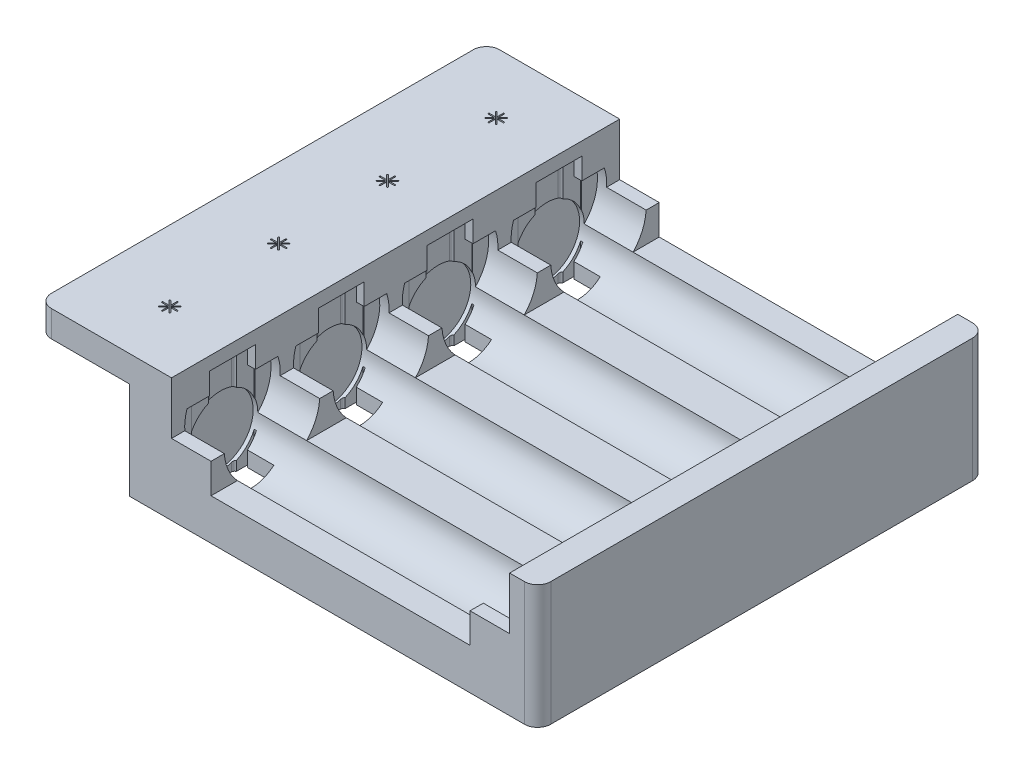
SolidWorks part; units mm, degrees
ref_plane "前视基准面" through (0, 0, 0) normal (0, 0, 1) x (1, 0, 0)
ref_plane "上视基准面" through (0, 0, 0) normal (0, 1, 0) x (1, 0, 0)
ref_plane "右视基准面" through (0, 0, 0) normal (1, 0, 0) x (0, 0, -1)
other "Configuration Table"
sketch "草图1" plane through (0, 0, 0) normal (0, 1, 0) x (1, 0, 0)
  line L1 (1.4739, 27.4794) -> (61.3689, 27.4794)
  line L2 (1.4739, 27.4794) -> (1.4739, -40.5206)
  line L3 (1.4739, -40.5206) -> (61.3689, -40.5206)
  line L4 (63.3689, 25.4794) -> (63.3689, -38.5206)
  arc A0 (61.3689, -40.5206) -> (63.3689, -38.5206) centre (61.3689, -38.5206) ccw
  arc A1 (61.3689, 27.4794) -> (63.3689, 25.4794) centre (61.3689, 25.4794) cw
  point P6 (63.3689, -40.5206)
  point P9 (63.3689, 27.4794)
  dimension "D3" = 2
  dimension "D1" = 68
  dimension "D2" = 61.895
extrude "凸台-拉伸1" add sketch "草图1" along normal blind 9.25
sketch "草图2" plane through (0, 9.25, 0) normal (0, 1, 0) x (1, 0, 0)
  line L0 (63.3689, -36.6531) -> (63.3689, -41.0442) construction
  line L1 (63.3689, -38.5206) -> (63.3689, 25.4794) construction
  line L2 (60.5082, -40.5206) -> (64.183, -40.5206) construction
  line L3 (1.4739, -40.5206) -> (61.3689, -40.5206) construction
  line L4 (54.4739, -29.5706) -> (54.4739, -32.9706) construction
  line L5 (63.3689, -40.5206) -> (54.4739, -40.5206) construction
  line L6 (63.3689, -40.5206) -> (63.3689, -31.2706) construction
  line L7 (63.3689, -31.2706) -> (54.4739, -31.2706) construction
  line L8 (54.4739, -40.5206) -> (54.4739, -31.2706) construction
  line L9 (54.9239, -29.5706) -> (54.9239, -32.9706)
  line L10 (54.0239, -29.5706) -> (54.0239, -32.9706)
  line L11 (54.4739, -13.0606) -> (54.4739, -16.4606) construction
  line L12 (54.9239, -13.0606) -> (54.9239, -16.4606)
  line L13 (54.0239, -13.0606) -> (54.0239, -16.4606)
  line L14 (54.4739, 3.4494) -> (54.4739, 0.0494) construction
  line L15 (54.9239, 3.4494) -> (54.9239, 0.0494)
  line L16 (54.0239, 3.4494) -> (54.0239, 0.0494)
  line L17 (54.4739, 19.9594) -> (54.4739, 16.5594) construction
  line L18 (54.9239, 19.9594) -> (54.9239, 16.5594)
  line L19 (54.0239, 19.9594) -> (54.0239, 16.5594)
  arc A0 (54.9239, -29.5706) -> (54.0239, -29.5706) centre (54.4739, -29.5706) ccw
  arc A1 (54.0239, -32.9706) -> (54.9239, -32.9706) centre (54.4739, -32.9706) ccw
  arc A2 (54.9239, -13.0606) -> (54.0239, -13.0606) centre (54.4739, -13.0606) ccw
  arc A3 (54.0239, -16.4606) -> (54.9239, -16.4606) centre (54.4739, -16.4606) ccw
  arc A4 (54.9239, 3.4494) -> (54.0239, 3.4494) centre (54.4739, 3.4494) ccw
  arc A5 (54.0239, 0.0494) -> (54.9239, 0.0494) centre (54.4739, 0.0494) ccw
  arc A6 (54.9239, 19.9594) -> (54.0239, 19.9594) centre (54.4739, 19.9594) ccw
  arc A7 (54.0239, 16.5594) -> (54.9239, 16.5594) centre (54.4739, 16.5594) ccw
  point P8 (63.3689, -40.5206)
  point P15 (54.4739, -31.2706)
  point P20 (54.4739, -29.1206)
  point P21 (54.4739, -33.4206)
  point P26 (54.4739, -14.7606)
  point P33 (54.4739, 1.7494)
  point P40 (54.4739, 18.2594)
  dimension "D3" = 0.45
  dimension "D1" = 8.895
  dimension "D2" = 9.25
  dimension "D4" = 4.3
  dimension "D5" = 4
extrude "切除-拉伸1" cut sketch "草图2" against normal blind 9.25
sketch "草图3" plane through (0, 9.25, 0) normal (0, 1, 0) x (1, 0, 0)
  line L0 (54.0239, -31.2706) -> (54.9239, -31.2706) construction
  line L1 (54.0239, -29.5706) -> (54.0239, -32.9706) construction
  line L2 (54.9239, -32.9706) -> (54.9239, -29.5706) construction
  line L3 (54.2989, -9.9356) -> (54.6489, -9.9356)
  line L4 (54.2989, -26.4456) -> (54.6489, -26.4456)
  line L5 (54.2989, -26.4456) -> (54.2989, -36.0956)
  line L6 (54.2989, -36.0956) -> (54.6489, -36.0956)
  line L7 (54.6489, -26.4456) -> (54.6489, -36.0956)
  line L8 (54.2989, -26.4456) -> (54.6489, -36.0956) construction
  line L9 (54.2989, -36.0956) -> (54.6489, -26.4456) construction
  line L10 (54.2989, -9.9356) -> (54.2989, -19.5856)
  line L11 (54.2989, -19.5856) -> (54.6489, -19.5856)
  line L12 (54.6489, -9.9356) -> (54.6489, -19.5856)
  line L13 (54.0239, -14.7606) -> (54.9239, -14.7606) construction
  line L14 (54.2989, -9.9356) -> (54.6489, -19.5856) construction
  line L15 (54.2989, -19.5856) -> (54.6489, -9.9356) construction
  line L16 (54.2989, 6.5744) -> (54.6489, 6.5744)
  line L17 (54.2989, 6.5744) -> (54.2989, -3.0756)
  line L18 (54.2989, -3.0756) -> (54.6489, -3.0756)
  line L19 (54.6489, 6.5744) -> (54.6489, -3.0756)
  line L20 (54.0239, 1.7494) -> (54.9239, 1.7494) construction
  line L21 (54.2989, 6.5744) -> (54.6489, -3.0756) construction
  line L22 (54.2989, -3.0756) -> (54.6489, 6.5744) construction
  line L23 (54.2989, 23.0844) -> (54.6489, 23.0844)
  line L24 (54.2989, 23.0844) -> (54.2989, 13.4344)
  line L25 (54.2989, 13.4344) -> (54.6489, 13.4344)
  line L26 (54.6489, 23.0844) -> (54.6489, 13.4344)
  line L27 (54.0239, 18.2594) -> (54.9239, 18.2594) construction
  line L28 (54.2989, 23.0844) -> (54.6489, 13.4344) construction
  line L29 (54.2989, 13.4344) -> (54.6489, 23.0844) construction
  point P6 (54.4739, -31.2706)
  point P15 (54.4739, -14.7606)
  point P22 (54.4739, 1.7494)
  point P29 (54.4739, 18.2594)
  dimension "D1" = 0.35
  dimension "D2" = 9.65
extrude "切除-拉伸4" cut sketch "草图3" against normal blind 5.25
sketch "草图6" plane through (0, 9.25, 0) normal (0, 1, 0) x (1, 0, 0)
  line L0 (54.0239, -36.5206) -> (54.0239, -26.0206)
  point P3 (54.0239, -31.2706)
sketch "草图7" plane through (0, 0, 0) normal (0, -1, 0) x (1, 0, 0)
  line L5 (61.3689, -27.4794) -> (1.4739, -27.4794)
  line L6 (63.3689, -25.4794) -> (63.3689, 38.5206)
  line L7 (61.3689, 40.5206) -> (1.4739, 40.5206)
  line L8 (1.4739, -27.4794) -> (1.4739, 40.5206)
  arc A0 (63.3689, 38.5206) -> (61.3689, 40.5206) centre (61.3689, 38.5206) ccw
  arc A1 (61.3689, -27.4794) -> (63.3689, -25.4794) centre (61.3689, -25.4794) ccw
  point P2 (63.3689, -27.4794)
  point P8 (63.3689, -27.4794)
  dimension "D1" = 2
  dimension "D2" = 2
extrude "凸台-拉伸2" add sketch "草图7" against normal blind 13.5
sketch "草图9" plane through (0, 13.5, 0) normal (0, 1, 0) x (1, 0, 0)
  line L0 (54.4739, -32.9706) -> (54.4739, -29.5706) construction
  line L2 (54.0239, -32.9706) -> (54.0239, -29.5706)
  line L4 (54.9239, -32.9706) -> (54.9239, -29.5706)
  line L5 (63.3689, -40.5206) -> (54.4739, -40.5206) construction
  line L6 (63.3689, -40.5206) -> (63.3689, -31.2706) construction
  line L7 (63.3689, -31.2706) -> (54.4739, -31.2706) construction
  line L8 (54.4739, -40.5206) -> (54.4739, -31.2706) construction
  line L9 (54.4739, -16.4606) -> (54.4739, -13.0606) construction
  line L10 (54.0239, -16.4606) -> (54.0239, -13.0606)
  line L11 (54.9239, -16.4606) -> (54.9239, -13.0606)
  line L12 (54.4739, 0.0494) -> (54.4739, 3.4494) construction
  line L13 (54.0239, 0.0494) -> (54.0239, 3.4494)
  line L14 (54.9239, 0.0494) -> (54.9239, 3.4494)
  line L15 (54.4739, 16.5594) -> (54.4739, 19.9594) construction
  line L16 (54.0239, 16.5594) -> (54.0239, 19.9594)
  line L17 (54.9239, 16.5594) -> (54.9239, 19.9594)
  arc A0 (54.0239, -32.9706) -> (54.9239, -32.9706) centre (54.4739, -32.9706) ccw
  arc A1 (54.9239, -29.5706) -> (54.0239, -29.5706) centre (54.4739, -29.5706) ccw
  arc A2 (54.0239, -16.4606) -> (54.9239, -16.4606) centre (54.4739, -16.4606) ccw
  arc A3 (54.9239, -13.0606) -> (54.0239, -13.0606) centre (54.4739, -13.0606) ccw
  arc A4 (54.0239, 0.0494) -> (54.9239, 0.0494) centre (54.4739, 0.0494) ccw
  arc A5 (54.9239, 3.4494) -> (54.0239, 3.4494) centre (54.4739, 3.4494) ccw
  arc A6 (54.0239, 16.5594) -> (54.9239, 16.5594) centre (54.4739, 16.5594) ccw
  arc A7 (54.9239, 19.9594) -> (54.0239, 19.9594) centre (54.4739, 19.9594) ccw
  point P2 (54.4739, -31.2706)
  point P7 (54.4739, -29.1206)
  point P8 (63.3689, -40.5206)
  point P9 (63.3689, -40.5206)
  point P14 (54.4739, -33.4206)
  point P18 (54.4739, -14.7606)
  point P25 (54.4739, 1.7494)
  point P32 (54.4739, 18.2594)
  dimension "D3" = 0.45
  dimension "D1" = 8.895
  dimension "D2" = 9.25
  dimension "D4" = 4.3
extrude "切除-拉伸5" cut sketch "草图9" against normal blind 13.5
sketch "草图10" plane through (0, 13.5, 0) normal (0, 1, 0) x (1, 0, 0)
  line L0 (54.3222, -19.5856) -> (54.6256, -19.5856)
  line L2 (54.3222, -19.5856) -> (54.3222, -9.9356)
  line L3 (54.3222, -36.0956) -> (54.6256, -36.0956)
  line L4 (54.3222, -36.0956) -> (54.3222, -26.4456)
  line L5 (54.3222, -26.4456) -> (54.6256, -26.4456)
  line L6 (54.6256, -36.0956) -> (54.6256, -26.4456)
  line L7 (54.3222, -36.0956) -> (54.6256, -26.4456) construction
  line L8 (54.3222, -26.4456) -> (54.6256, -36.0956) construction
  line L9 (54.3222, -9.9356) -> (54.6256, -9.9356)
  line L10 (54.6256, -19.5856) -> (54.6256, -9.9356)
  line L11 (54.3222, -19.5856) -> (54.6256, -9.9356) construction
  line L12 (54.3222, -9.9356) -> (54.6256, -19.5856) construction
  line L13 (54.3222, -3.0756) -> (54.6256, -3.0756)
  line L14 (54.3222, -3.0756) -> (54.3222, 6.5744)
  line L15 (54.3222, 6.5744) -> (54.6256, 6.5744)
  line L16 (54.6256, -3.0756) -> (54.6256, 6.5744)
  line L17 (54.3222, -3.0756) -> (54.6256, 6.5744) construction
  line L18 (54.3222, 6.5744) -> (54.6256, -3.0756) construction
  line L19 (54.3222, 13.4344) -> (54.6256, 13.4344)
  line L20 (54.3222, 13.4344) -> (54.3222, 23.0844)
  line L21 (54.3222, 23.0844) -> (54.6256, 23.0844)
  line L22 (54.6256, 13.4344) -> (54.6256, 23.0844)
  line L23 (54.3222, 13.4344) -> (54.6256, 23.0844) construction
  line L24 (54.3222, 23.0844) -> (54.6256, 13.4344) construction
  point P3 (54.4739, -14.7606)
  point P5 (54.4739, -31.2706)
  point P13 (54.4739, 1.7494)
  point P18 (54.4739, 18.2594)
  dimension "D1" = 0.3034
extrude "切除-拉伸6" cut sketch "草图10" against normal blind 13.5
sketch "草图11" plane through (0, 13.5, 0) normal (0, 1, 0) x (1, 0, 0)
  line L0 (6.4592, -32.9706) -> (6.4592, -29.5706) construction
  line L1 (6.0092, -32.9706) -> (6.0092, -29.5706)
  line L2 (6.9092, -32.9706) -> (6.9092, -29.5706)
  line L3 (6.2927, -19.5856) -> (6.6256, -19.5856)
  line L4 (6.2927, -36.0956) -> (6.6256, -36.0956)
  line L5 (6.2927, -36.0956) -> (6.2927, -26.4456)
  line L6 (6.2927, -26.4456) -> (6.6256, -26.4456)
  line L7 (6.6256, -36.0956) -> (6.6256, -26.4456)
  line L8 (6.2927, -36.0956) -> (6.6256, -26.4456) construction
  line L9 (6.2927, -26.4456) -> (6.6256, -36.0956) construction
  line L10 (6.2927, -19.5856) -> (6.2927, -9.9356)
  line L11 (6.2927, -9.9356) -> (6.6256, -9.9356)
  line L12 (6.6256, -19.5856) -> (6.6256, -9.9356)
  line L13 (6.2927, -19.5856) -> (6.6256, -9.9356) construction
  line L14 (6.2927, -9.9356) -> (6.6256, -19.5856) construction
  line L15 (6.4592, -16.4606) -> (6.4592, -13.0606) construction
  line L16 (6.0092, -16.4606) -> (6.0092, -13.0606)
  line L17 (6.9092, -16.4606) -> (6.9092, -13.0606)
  line L18 (6.2927, -3.0756) -> (6.6256, -3.0756)
  line L19 (6.2927, -3.0756) -> (6.2927, 6.5744)
  line L20 (6.2927, 6.5744) -> (6.6256, 6.5744)
  line L21 (6.6256, -3.0756) -> (6.6256, 6.5744)
  line L22 (6.2927, -3.0756) -> (6.6256, 6.5744) construction
  line L23 (6.2927, 6.5744) -> (6.6256, -3.0756) construction
  line L24 (6.4592, 0.0494) -> (6.4592, 3.4494) construction
  line L25 (6.0092, 0.0494) -> (6.0092, 3.4494)
  line L26 (6.9092, 0.0494) -> (6.9092, 3.4494)
  line L27 (6.2927, 13.4344) -> (6.6256, 13.4344)
  line L28 (6.2927, 13.4344) -> (6.2927, 23.0844)
  line L29 (6.2927, 23.0844) -> (6.6256, 23.0844)
  line L30 (6.6256, 13.4344) -> (6.6256, 23.0844)
  line L31 (6.2927, 13.4344) -> (6.6256, 23.0844) construction
  line L32 (6.2927, 23.0844) -> (6.6256, 13.4344) construction
  line L33 (6.4592, 16.5594) -> (6.4592, 19.9594) construction
  line L34 (6.0092, 16.5594) -> (6.0092, 19.9594)
  line L35 (6.9092, 16.5594) -> (6.9092, 19.9594)
  arc A0 (6.0092, -32.9706) -> (6.9092, -32.9706) centre (6.4592, -32.9706) ccw
  arc A1 (6.9092, -29.5706) -> (6.0092, -29.5706) centre (6.4592, -29.5706) ccw
  arc A2 (6.0092, -16.4606) -> (6.9092, -16.4606) centre (6.4592, -16.4606) ccw
  arc A3 (6.9092, -13.0606) -> (6.0092, -13.0606) centre (6.4592, -13.0606) ccw
  arc A4 (6.0092, 0.0494) -> (6.9092, 0.0494) centre (6.4592, 0.0494) ccw
  arc A5 (6.9092, 3.4494) -> (6.0092, 3.4494) centre (6.4592, 3.4494) ccw
  arc A6 (6.0092, 16.5594) -> (6.9092, 16.5594) centre (6.4592, 16.5594) ccw
  arc A7 (6.9092, 19.9594) -> (6.0092, 19.9594) centre (6.4592, 19.9594) ccw
  point P2 (6.4592, -31.2706)
  point P7 (6.4592, -29.1206)
  point P8 (6.4592, -33.4206)
  point P9 (6.4592, -31.2706)
  point P19 (6.4592, -14.7606)
  point P24 (6.4592, -14.7606)
  point P31 (6.4592, 1.7494)
  point P36 (6.4592, 1.7494)
  point P43 (6.4592, 18.2594)
  point P48 (6.4592, 18.2594)
  dimension "D2" = 0.45
  dimension "D1" = 4.3
  dimension "D3" = 0
  dimension "D4" = 48
  dimension "D5" = 4
extrude "切除-拉伸7" cut sketch "草图11" against normal blind 13.5 contours L2 A1 L7 A0 | L5 A1 L1 A0 | A0 L5 L4 L7 | A1 L7 L6 L5 | A3 L12 L11 L10 | A2 L10 L3 L12 | L26 A5 L21 A4 | A7 L30 L29 L28 | A6 L28 L27 L30 | L28 A7 L34 A6 | L7 A1 L5 A0 | L12 A3 L10 A2 | L19 A5 L25 A4 | L16 A3 L17 A2 | L20 L21 L18 L19 | L35 A7 L34 A6 | L30 L29 L28 L27 region at (6.1547, 13.5, 31.2706) region at (6.4592, 13.5, 34.7529) region at (6.4592, 13.5, 31.2706) region at (6.4592, 13.5, 27.7884) region at (6.7637, 13.5, 31.2706) region at (6.4592, 13.5, 18.2429) region at (6.4592, 13.5, 14.7606) region at (6.4592, 13.5, 11.2784) region at (6.1547, 13.5, -1.7494) region at (6.7637, 13.5, -1.7494) region at (6.4592, 13.5, -14.7771) region at (6.1547, 13.5, -18.2594) region at (6.4592, 13.5, -21.7416)
sketch "草图13" plane through (0, 13.5, 0) normal (0, 1, 0) x (1, 0, 0)
  line L0 (6.2927, -36.0956) -> (6.2927, -40.5206) construction
  line L1 (61.3689, -40.5206) -> (1.4739, -40.5206) construction
  line L2 (6.6256, -36.0956) -> (6.6256, -40.5206) construction
  line L3 (54.3222, -36.0956) -> (54.3222, -40.5206) construction
  line L4 (54.6256, -36.0956) -> (54.6256, -40.5206) construction
sketch "草图14" plane through (0, 0, 40.5206) normal (0, 0, 1) x (1, 0, 0)
  line L0 (61.3689, 13.5) -> (1.4739, 13.5) construction
  line L1 (7.8256, 13.5) -> (53.1222, 13.5)
  line L2 (7.8256, 13.5) -> (7.8256, 6.25)
  line L3 (7.8256, 6.25) -> (53.1222, 6.25)
  line L4 (53.1222, 13.5) -> (53.1222, 6.25)
  point P6 (0, 0)
  dimension "D1" = 1.2
  dimension "D2" = 1.2
  dimension "D3" = 7.25
extrude "切除-拉伸8" cut sketch "草图14" against normal blind 78.5
sketch "草图15" plane through (0, 13.5, 0) normal (0, 1, 0) x (1, 0, 0)
  line L0 (7.8256, 27.4794) -> (7.8256, -40.5206) construction
  line L1 (7.8256, 27.4794) -> (7.8256, -40.5206) construction
  point P0 (7.8256, -31.2706)
  point P1 (7.8256, -14.7606)
  point P4 (7.8256, 1.7494)
  point P7 (7.8256, 18.2594)
ref_plane "基准面1" through (7.8256, 0, 0) normal (1, 0, 0) x (0, 0, -1)
sketch "草图17" plane through (7.8256, 0, 0) normal (1, 0, 0) x (0, 0, -1)
  circle A0 centre (-31.2706, 6.25) radius 5.25
  circle A1 centre (-14.7606, 6.25) radius 5.25
  circle A2 centre (1.7494, 6.25) radius 5.25
  circle A3 centre (18.2594, 6.25) radius 5.25
  dimension "D1" = 10.5
extrude "切除-拉伸9" cut sketch "草图17" along normal blind 46.5 and the other way blind 2.1105
sketch "草图18" plane through (0, 0, 0) normal (0, -1, 0) x (1, 0, 0)
  line L0 (6.6256, 34.7422) -> (6.6256, 27.7991)
  line L1 (6.6256, 34.7422) -> (10.6286, 34.7422)
  line L2 (6.6256, 27.7991) -> (10.6286, 27.7991)
  line L3 (10.6286, 34.7422) -> (10.6286, 27.7991)
  line L4 (6.6256, 36.0956) -> (6.6256, 33.3887) construction
  line L5 (6.6256, 29.1525) -> (6.6256, 26.4456) construction
  line L6 (6.6256, 18.2322) -> (6.6256, 11.2891)
  line L7 (6.6256, 18.2322) -> (10.6286, 18.2322)
  line L8 (10.6286, 18.2322) -> (10.6286, 11.2891)
  line L9 (6.6256, 11.2891) -> (10.6286, 11.2891)
  line L10 (6.6256, 1.7222) -> (6.6256, -5.2209)
  line L11 (6.6256, 1.7222) -> (10.6286, 1.7222)
  line L12 (10.6286, 1.7222) -> (10.6286, -5.2209)
  line L13 (6.6256, -5.2209) -> (10.6286, -5.2209)
  line L14 (6.6256, -14.7878) -> (6.6256, -21.7309)
  line L15 (6.6256, -14.7878) -> (10.6286, -14.7878)
  line L16 (10.6286, -14.7878) -> (10.6286, -21.7309)
  line L17 (6.6256, -21.7309) -> (10.6286, -21.7309)
extrude "切除-拉伸10" cut sketch "草图18" against normal blind 2.36
sketch "草图19" plane through (0, 0, 0) normal (0, -1, 0) x (1, 0, 0)
  line L0 (54.3222, 34.745) -> (54.3222, 27.7963)
  line L1 (54.3222, 34.745) -> (50.3222, 34.745)
  line L2 (54.3222, 27.7963) -> (50.3222, 27.7963)
  line L3 (50.3222, 34.745) -> (50.3222, 27.7963)
  line L4 (54.3222, 33.3943) -> (54.3222, 36.0956) construction
  line L5 (54.3222, 26.4456) -> (54.3222, 29.147) construction
  line L6 (54.3222, 18.235) -> (54.3222, 11.2863)
  line L7 (54.3222, 18.235) -> (50.3222, 18.235)
  line L8 (54.3222, 11.2863) -> (50.3222, 11.2863)
  line L9 (50.3222, 18.235) -> (50.3222, 11.2863)
  line L10 (54.3222, 1.725) -> (54.3222, -5.2237)
  line L11 (54.3222, 1.725) -> (50.3222, 1.725)
  line L12 (54.3222, -5.2237) -> (50.3222, -5.2237)
  line L13 (50.3222, 1.725) -> (50.3222, -5.2237)
  line L14 (54.3222, -14.785) -> (54.3222, -21.7337)
  line L15 (54.3222, -14.785) -> (50.3222, -14.785)
  line L16 (54.3222, -21.7337) -> (50.3222, -21.7337)
  line L17 (50.3222, -14.785) -> (50.3222, -21.7337)
extrude "切除-拉伸11" cut sketch "草图19" against normal blind 2.36
sketch "草图20" plane through (0, 13.5, 0) normal (0, 1, 0) x (1, 0, 0)
  line L0 (60.3222, -36.0956) -> (60.6256, -36.0956)
  line L1 (60.6256, -36.0956) -> (60.6256, -33.3943)
  line L2 (60.3222, -33.3943) -> (60.3222, -36.0956)
  line L3 (60.9239, -32.9706) -> (60.9239, -29.5706)
  line L4 (60.0239, -29.5706) -> (60.0239, -32.9706)
  line L5 (60.6256, -29.147) -> (60.6256, -26.4456)
  line L6 (60.6256, -26.4456) -> (60.3222, -26.4456)
  line L7 (60.3222, -26.4456) -> (60.3222, -29.147)
  line L8 (60.3222, -19.5856) -> (60.6256, -19.5856)
  line L9 (60.6256, -19.5856) -> (60.6256, -16.8843)
  line L10 (60.3222, -16.8843) -> (60.3222, -19.5856)
  line L11 (60.9239, -16.4606) -> (60.9239, -13.0606)
  line L12 (60.0239, -13.0606) -> (60.0239, -16.4606)
  line L13 (60.6256, -12.637) -> (60.6256, -9.9356)
  line L14 (60.6256, -9.9356) -> (60.3222, -9.9356)
  line L15 (60.3222, -9.9356) -> (60.3222, -12.637)
  line L16 (60.3222, -3.0756) -> (60.6256, -3.0756)
  line L17 (60.6256, -3.0756) -> (60.6256, -0.3743)
  line L18 (60.3222, -0.3743) -> (60.3222, -3.0756)
  line L19 (60.9239, 0.0494) -> (60.9239, 3.4494)
  line L20 (60.0239, 3.4494) -> (60.0239, 0.0494)
  line L21 (60.6256, 3.873) -> (60.6256, 6.5744)
  line L22 (60.6256, 6.5744) -> (60.3222, 6.5744)
  line L23 (60.3222, 6.5744) -> (60.3222, 3.873)
  line L24 (54.3222, -19.5856) -> (54.6256, -19.5856)
  line L25 (54.6256, -19.5856) -> (54.6256, -16.8843)
  line L26 (54.3222, -16.8843) -> (54.3222, -19.5856)
  line L27 (54.9239, -16.4606) -> (54.9239, -13.0606)
  line L28 (54.0239, -13.0606) -> (54.0239, -16.4606)
  line L29 (54.6256, -12.637) -> (54.6256, -9.9356)
  line L30 (54.6256, -9.9356) -> (54.3222, -9.9356)
  line L31 (54.3222, -9.9356) -> (54.3222, -12.637)
  line L32 (54.3222, -19.5856) -> (54.6256, -19.5856)
  line L33 (54.6256, -19.5856) -> (54.6256, -16.8843)
  line L34 (54.3222, -16.8843) -> (54.3222, -19.5856)
  line L35 (54.9239, -16.4606) -> (54.9239, -13.0606)
  line L36 (54.0239, -13.0606) -> (54.0239, -16.4606)
  line L37 (54.6256, -12.637) -> (54.6256, -9.9356)
  line L38 (54.6256, -9.9356) -> (54.3222, -9.9356)
  line L39 (54.3222, -9.9356) -> (54.3222, -12.637)
  line L40 (60.3222, 13.4344) -> (60.6256, 13.4344)
  line L41 (60.6256, 13.4344) -> (60.6256, 16.1357)
  line L42 (60.3222, 16.1357) -> (60.3222, 13.4344)
  line L43 (60.9239, 16.5594) -> (60.9239, 19.9594)
  line L44 (60.0239, 19.9594) -> (60.0239, 16.5594)
  line L45 (60.6256, 20.383) -> (60.6256, 23.0844)
  line L46 (60.6256, 23.0844) -> (60.3222, 23.0844)
  line L47 (60.3222, 23.0844) -> (60.3222, 20.383)
  arc A0 (60.6256, -33.3943) -> (60.9239, -32.9706) centre (60.4739, -32.9706) ccw
  arc A1 (60.0239, -32.9706) -> (60.3222, -33.3943) centre (60.4739, -32.9706) ccw
  arc A2 (60.9239, -29.5706) -> (60.6256, -29.147) centre (60.4739, -29.5706) ccw
  arc A3 (60.3222, -29.147) -> (60.0239, -29.5706) centre (60.4739, -29.5706) ccw
  arc A4 (60.6256, -16.8843) -> (60.9239, -16.4606) centre (60.4739, -16.4606) ccw
  arc A5 (60.0239, -16.4606) -> (60.3222, -16.8843) centre (60.4739, -16.4606) ccw
  arc A6 (60.9239, -13.0606) -> (60.6256, -12.637) centre (60.4739, -13.0606) ccw
  arc A7 (60.3222, -12.637) -> (60.0239, -13.0606) centre (60.4739, -13.0606) ccw
  arc A8 (60.6256, -0.3743) -> (60.9239, 0.0494) centre (60.4739, 0.0494) ccw
  arc A9 (60.0239, 0.0494) -> (60.3222, -0.3743) centre (60.4739, 0.0494) ccw
  arc A10 (60.9239, 3.4494) -> (60.6256, 3.873) centre (60.4739, 3.4494) ccw
  arc A11 (60.3222, 3.873) -> (60.0239, 3.4494) centre (60.4739, 3.4494) ccw
  arc A12 (54.6256, -16.8843) -> (54.9239, -16.4606) centre (54.4739, -16.4606) ccw
  arc A13 (54.0239, -16.4606) -> (54.3222, -16.8843) centre (54.4739, -16.4606) ccw
  arc A14 (54.9239, -13.0606) -> (54.6256, -12.637) centre (54.4739, -13.0606) ccw
  arc A15 (54.3222, -12.637) -> (54.0239, -13.0606) centre (54.4739, -13.0606) ccw
  arc A16 (54.6256, -16.8843) -> (54.9239, -16.4606) centre (54.4739, -16.4606) ccw
  arc A17 (54.0239, -16.4606) -> (54.3222, -16.8843) centre (54.4739, -16.4606) ccw
  arc A18 (54.9239, -13.0606) -> (54.6256, -12.637) centre (54.4739, -13.0606) ccw
  arc A19 (54.3222, -12.637) -> (54.0239, -13.0606) centre (54.4739, -13.0606) ccw
  arc A20 (60.6256, 16.1357) -> (60.9239, 16.5594) centre (60.4739, 16.5594) ccw
  arc A21 (60.0239, 16.5594) -> (60.3222, 16.1357) centre (60.4739, 16.5594) ccw
  arc A22 (60.9239, 19.9594) -> (60.6256, 20.383) centre (60.4739, 19.9594) ccw
  arc A23 (60.3222, 20.383) -> (60.0239, 19.9594) centre (60.4739, 19.9594) ccw
  dimension "D2" = 6
  dimension "D3" = 0
  dimension "D1" = 0
extrude "切除-拉伸12" cut sketch "草图20" against normal blind 70.36
sketch "草图21" plane through (0, 13.5, 0) normal (0, 1, 0) x (1, 0, 0)
  line L8 (61.3689, 27.4794) -> (53.1222, 27.4794)
  line L9 (53.1222, 27.4794) -> (53.1222, -40.5206)
  line L10 (53.1222, -40.5206) -> (61.3689, -40.5206)
  line L11 (63.3689, -38.5206) -> (63.3689, 25.4794)
  line L12 (61.3689, 27.4794) -> (53.1222, 27.4794)
  line L13 (53.1222, 27.4794) -> (53.1222, -40.5206)
  line L14 (53.1222, -40.5206) -> (61.3689, -40.5206)
  line L15 (63.3689, -38.5206) -> (63.3689, 25.4794)
  arc A4 (61.3689, -40.5206) -> (63.3689, -38.5206) centre (61.3689, -38.5206) ccw
  arc A5 (63.3689, 25.4794) -> (61.3689, 27.4794) centre (61.3689, 25.4794) ccw
  arc A6 (61.3689, -40.5206) -> (63.3689, -38.5206) centre (61.3689, -38.5206) ccw
  arc A7 (63.3689, 25.4794) -> (61.3689, 27.4794) centre (61.3689, 25.4794) ccw
  dimension "D1" = 0
extrude "凸台-拉伸3" add sketch "草图21" along normal blind 5.25
ref_plane "基准面2" through (53.1222, 0, 0) normal (-1, 0, 0) x (0, 0, 1)
sketch "草图22" plane through (53.1222, 0, 0) normal (-1, 0, 0) x (0, 0, 1)
  line L0 (-23.5094, 6.25) -> (-13.0094, 6.25)
  line L1 (-18.2594, 6.25) -> (-18.2594, 12.686)
  arc A0 (-13.0094, 6.25) -> (-23.5094, 6.25) centre (-18.2594, 6.25) ccw construction
  arc A1 (-23.0844, 8.3193) -> (-23.0844, 4.1807) centre (-18.2594, 6.25) ccw construction
  circle A2 centre (-18.2594, 11.25) radius 7.25
  circle A3 centre (-1.7494, 11.25) radius 7.25
  circle A4 centre (14.7606, 11.25) radius 7.25
  circle A5 centre (31.2706, 11.25) radius 7.25
  point P0 (-23.5094, 6.25)
  point P1 (-13.0094, 6.25)
  dimension "D1" = 4
extrude "切除-拉伸14" cut sketch "草图22" along normal blind 46.7 and the other way blind 7.4 contours A3 | A5 | A2 | A3 | A4 region at (53.1222, 11.25, -1.7494) region at (53.1222, 11.25, 31.2706)
sketch "草图24" plane through (7.8256, 0, 0) normal (1, 0, 0) x (0, 0, -1)
  line L0 (27.4794, 10.7858) -> (-40.5206, 10.7858)
  line L1 (27.4794, 13.5) -> (27.4794, 6.25) construction
  line L2 (-40.5206, 13.5) -> (-40.5206, 6.25) construction
  line L3 (-40.5206, 10.7858) -> (-40.5206, 13.5)
  line L4 (-40.5206, 13.5) -> (27.4794, 13.5)
  line L5 (27.4794, 13.5) -> (27.4794, 10.7858)
  arc A0 (23.5094, 6.25) -> (25.1514, 13.5) centre (18.2594, 11.25) ccw construction
  point P0 (25.4945, 10.7858)
  point P14 (0, 0)
  point P15 (0, 0)
sketch "草图25" plane through (0, 0, 0) normal (0, -1, 0) x (1, 0, 0)
  line L0 (60.2756, -21.7309) -> (56.9367, -21.7309)
  line L1 (60.2756, -14.7878) -> (56.9367, -14.7878)
  line L2 (56.9367, -21.7309) -> (56.9367, -14.7878)
  line L3 (60.2756, 1.7222) -> (56.9367, 1.7222)
  line L4 (56.9367, -5.2209) -> (56.9367, 1.7222)
  line L5 (60.2756, 3.0756) -> (60.2756, 1.7222)
  line L6 (60.6256, 3.0756) -> (60.2756, 3.0756)
  line L7 (60.6256, 0.3687) -> (60.6256, 3.0756)
  line L8 (60.2756, -13.4344) -> (60.2756, -14.7878)
  line L9 (60.6256, -13.4344) -> (60.2756, -13.4344)
  line L10 (60.6256, -16.1413) -> (60.6256, -13.4344)
  line L11 (60.9241, -3.4494) -> (60.9241, -0.0494)
  line L12 (60.2756, -21.7309) -> (60.2756, -23.0844)
  line L13 (60.2756, -23.0844) -> (60.6256, -23.0844)
  line L14 (60.6256, -23.0844) -> (60.6256, -20.3775)
  line L15 (60.9241, -19.9594) -> (60.9241, -16.5594)
  line L16 (6.6256, -6.5744) -> (6.6256, -5.2209)
  line L17 (6.2927, -6.5744) -> (6.6256, -6.5744)
  line L18 (6.2927, -3.8675) -> (6.2927, -6.5744)
  line L19 (10.6286, 1.7222) -> (6.6256, 1.7222)
  line L20 (6.6256, 1.7222) -> (6.6256, 3.0756)
  line L21 (6.6256, 3.0756) -> (6.2927, 3.0756)
  line L22 (6.2927, 3.0756) -> (6.2927, 0.3687)
  line L23 (6.0092, -0.0494) -> (6.0092, -3.4494)
  line L24 (6.6256, -6.5744) -> (6.6256, -5.2209)
  line L25 (6.2927, -6.5744) -> (6.6256, -6.5744)
  line L26 (6.2927, -3.8675) -> (6.2927, -6.5744)
  line L27 (60.6256, -6.5744) -> (60.6256, -3.8675)
  line L28 (6.6256, 1.7222) -> (6.6256, 3.0756)
  line L29 (6.6256, 3.0756) -> (6.2927, 3.0756)
  line L30 (6.2927, 3.0756) -> (6.2927, 0.3687)
  line L31 (6.0092, -0.0494) -> (6.0092, -3.4494)
  line L32 (60.2756, -6.5744) -> (60.6256, -6.5744)
  line L33 (60.2756, -5.2209) -> (60.2756, -6.5744)
  line L34 (60.2756, -5.2209) -> (56.9367, -5.2209)
  line L35 (60.2756, 18.2322) -> (56.9367, 18.2322)
  line L36 (56.9367, 11.2891) -> (56.9367, 18.2322)
  line L37 (60.2756, 19.5856) -> (60.2756, 18.2322)
  line L38 (60.6256, 19.5856) -> (60.2756, 19.5856)
  line L39 (60.6256, 16.8787) -> (60.6256, 19.5856)
  line L40 (60.9241, 13.0606) -> (60.9241, 16.4606)
  line L41 (60.6256, 9.9356) -> (60.6256, 12.6425)
  line L42 (60.2756, 9.9356) -> (60.6256, 9.9356)
  line L43 (60.2756, 11.2891) -> (60.2756, 9.9356)
  line L44 (60.2756, 11.2891) -> (56.9367, 11.2891)
  line L45 (60.2756, 34.7422) -> (56.9367, 34.7422)
  line L46 (56.9367, 27.7991) -> (56.9367, 34.7422)
  line L47 (60.2756, 36.0956) -> (60.2756, 34.7422)
  line L48 (60.6256, 36.0956) -> (60.2756, 36.0956)
  line L49 (60.6256, 33.3887) -> (60.6256, 36.0956)
  line L50 (60.9241, 29.5706) -> (60.9241, 32.9706)
  line L51 (60.6256, 26.4456) -> (60.6256, 29.1525)
  line L52 (60.2756, 26.4456) -> (60.6256, 26.4456)
  line L53 (60.2756, 27.7991) -> (60.2756, 26.4456)
  line L54 (60.2756, 27.7991) -> (56.9367, 27.7991)
  arc A0 (60.9241, -0.0494) -> (60.6256, 0.3687) centre (60.4741, -0.055) ccw
  arc A1 (60.6256, -3.8675) -> (60.9241, -3.4494) centre (60.4741, -3.4437) ccw
  arc A2 (60.9241, -16.5594) -> (60.6256, -16.1413) centre (60.4741, -16.565) ccw
  arc A3 (60.6256, -20.3775) -> (60.9241, -19.9594) centre (60.4741, -19.9537) ccw
  arc A4 (6.0092, -3.4494) -> (6.2927, -3.8675) centre (6.4592, -3.4494) ccw
  arc A5 (6.2927, 0.3687) -> (6.0092, -0.0494) centre (6.4592, -0.0494) ccw
  arc A6 (6.0092, -3.4494) -> (6.2927, -3.8675) centre (6.4592, -3.4494) ccw
  arc A7 (6.2927, 0.3687) -> (6.0092, -0.0494) centre (6.4592, -0.0494) ccw
  arc A8 (60.9241, 16.4606) -> (60.6256, 16.8787) centre (60.4741, 16.455) ccw
  arc A9 (60.6256, 12.6425) -> (60.9241, 13.0606) centre (60.4741, 13.0663) ccw
  arc A10 (60.9241, 32.9706) -> (60.6256, 33.3887) centre (60.4741, 32.965) ccw
  arc A11 (60.6256, 29.1525) -> (60.9241, 29.5706) centre (60.4741, 29.5763) ccw
  dimension "D2" = 6
  dimension "D3" = 0
  dimension "D4" = 4
  dimension "D1" = 0
extrude "切除-拉伸16" cut sketch "草图25" against normal blind 55.7 contours L14 A3 L15 A2 L10 L9 L8 L1 L2 L0 L12 L13 | L27 A1 L11 A0 L7 L6 L5 L3 L4 L34 L33 L32 | L41 A9 L40 A8 L39 L38 L37 L35 L36 L44 L43 L42 | L51 A11 L50 A10 L49 L48 L47 L45 L46 L54 L53 L52 region at (58.9238, 0, -18.2594) region at (58.9238, 0, -1.7494) region at (58.9238, 0, 14.7606) region at (58.9238, 0, 31.2706)
sketch "草图27" plane through (53.1222, 0, 0) normal (-1, 0, 0) x (0, 0, 1)
  line L1 (-27.4794, 18.75) -> (40.5206, 18.75)
  line L2 (-27.4794, 18.75) -> (-27.4794, 10.7858)
  line L3 (-27.4794, 10.7858) -> (40.5206, 10.7858)
  line L4 (40.5206, 18.75) -> (40.5206, 10.7858)
extrude "切除-拉伸17" cut sketch "草图27" against normal blind 6
sketch "草图28" plane through (7.8256, 0, 0) normal (1, 0, 0) x (0, 0, -1)
  line L1 (27.4794, 13.5) -> (-40.5206, 13.5)
  line L2 (27.4794, 13.5) -> (27.4794, 18.75)
  line L3 (27.4794, 18.75) -> (-40.5206, 18.75)
  line L4 (-40.5206, 13.5) -> (-40.5206, 18.75)
extrude "凸台-拉伸4" add sketch "草图28" against normal up to surface (6.3517 mm away) up to face at (1.4739, 6.75, 6.5206)
sketch "草图29" plane through (0, 0, 0) normal (0, -1, 0) x (1, 0, 0)
  line L10 (10.6286, 11.2891) -> (10.6286, 18.2322)
  line L11 (10.6286, 18.2322) -> (6.6256, 18.2322)
  line L12 (6.6256, 18.2322) -> (6.6256, 19.5856)
  line L13 (6.6256, 19.5856) -> (6.2927, 19.5856)
  line L14 (6.2927, 19.5856) -> (6.2927, 16.8787)
  line L15 (6.0092, 16.4606) -> (6.0092, 13.0606)
  line L16 (6.2927, 12.6425) -> (6.2927, 9.9356)
  line L17 (6.2927, 9.9356) -> (6.6256, 9.9356)
  line L18 (6.6256, 9.9356) -> (6.6256, 11.2891)
  line L19 (6.6256, 11.2891) -> (10.6286, 11.2891)
  line L20 (10.6286, 27.7991) -> (10.6286, 34.7422)
  line L21 (10.6286, 34.7422) -> (6.6256, 34.7422)
  line L22 (6.6256, 34.7422) -> (6.6256, 36.0956)
  line L23 (6.6256, 36.0956) -> (6.2927, 36.0956)
  line L24 (6.2927, 36.0956) -> (6.2927, 33.3887)
  line L25 (6.0092, 32.9706) -> (6.0092, 29.5706)
  line L26 (6.2927, 29.1525) -> (6.2927, 26.4456)
  line L27 (6.2927, 26.4456) -> (6.6256, 26.4456)
  line L28 (6.6256, 26.4456) -> (6.6256, 27.7991)
  line L29 (6.6256, 27.7991) -> (10.6286, 27.7991)
  line L30 (10.6286, 27.7991) -> (10.6286, 34.7422)
  line L31 (10.6286, 34.7422) -> (6.6256, 34.7422)
  line L32 (6.6256, 34.7422) -> (6.6256, 36.0956)
  line L33 (6.6256, 36.0956) -> (6.2927, 36.0956)
  line L34 (6.2927, 36.0956) -> (6.2927, 33.3887)
  line L35 (6.0092, 32.9706) -> (6.0092, 29.5706)
  line L36 (6.2927, 29.1525) -> (6.2927, 26.4456)
  line L37 (6.2927, 26.4456) -> (6.6256, 26.4456)
  line L38 (6.6256, 26.4456) -> (6.6256, 27.7991)
  line L39 (6.6256, 27.7991) -> (10.6286, 27.7991)
  line L40 (10.6286, -5.2209) -> (10.6286, 1.7222)
  line L41 (10.6286, 1.7222) -> (6.6256, 1.7222)
  line L42 (6.6256, 1.7222) -> (6.6256, 3.0756)
  line L43 (6.6256, 3.0756) -> (6.2927, 3.0756)
  line L44 (6.2927, 3.0756) -> (6.2927, 0.3687)
  line L45 (6.0092, -0.0494) -> (6.0092, -3.4494)
  line L46 (6.2927, -3.8675) -> (6.2927, -6.5744)
  line L47 (6.2927, -6.5744) -> (6.6256, -6.5744)
  line L48 (6.6256, -6.5744) -> (6.6256, -5.2209)
  line L49 (6.6256, -5.2209) -> (10.6286, -5.2209)
  line L50 (10.6286, -21.7309) -> (10.6286, -14.7878)
  line L51 (10.6286, -14.7878) -> (6.6256, -14.7878)
  line L52 (6.6256, -14.7878) -> (6.6256, -13.4344)
  line L53 (6.6256, -13.4344) -> (6.2927, -13.4344)
  line L54 (6.2927, -13.4344) -> (6.2927, -16.1413)
  line L55 (6.0092, -16.5594) -> (6.0092, -19.9594)
  line L56 (6.2927, -20.3775) -> (6.2927, -23.0844)
  line L57 (6.2927, -23.0844) -> (6.6256, -23.0844)
  line L58 (6.6256, -23.0844) -> (6.6256, -21.7309)
  line L59 (6.6256, -21.7309) -> (10.6286, -21.7309)
  arc A2 (6.2927, 16.8787) -> (6.0092, 16.4606) centre (6.4592, 16.4606) ccw
  arc A3 (6.0092, 13.0606) -> (6.2927, 12.6425) centre (6.4592, 13.0606) ccw
  arc A4 (6.2927, 33.3887) -> (6.0092, 32.9706) centre (6.4592, 32.9706) ccw
  arc A5 (6.0092, 29.5706) -> (6.2927, 29.1525) centre (6.4592, 29.5706) ccw
  arc A6 (6.2927, 33.3887) -> (6.0092, 32.9706) centre (6.4592, 32.9706) ccw
  arc A7 (6.0092, 29.5706) -> (6.2927, 29.1525) centre (6.4592, 29.5706) ccw
  arc A8 (6.2927, 0.3687) -> (6.0092, -0.0494) centre (6.4592, -0.0494) ccw
  arc A9 (6.0092, -3.4494) -> (6.2927, -3.8675) centre (6.4592, -3.4494) ccw
  arc A10 (6.2927, -16.1413) -> (6.0092, -16.5594) centre (6.4592, -16.5594) ccw
  arc A11 (6.0092, -19.9594) -> (6.2927, -20.3775) centre (6.4592, -19.9594) ccw
  dimension "D1" = 0
extrude "切除-拉伸18" cut sketch "草图29" against normal up to surface (18.75 mm away) up to face at (4.6498, 18.75, 6.5206)
sketch "草图31" plane through (7.8256, 0, 0) normal (1, 0, 0) x (0, 0, -1)
  line L27 (-38.1627, 13.5) -> (-34.7422, 13.5)
  line L28 (-34.7422, 13.5) -> (-34.7422, 18.75)
  line L29 (-34.7422, 18.75) -> (-40.5206, 18.75)
  line L30 (-40.5206, 18.75) -> (-40.5206, 6.25)
  line L31 (-40.5206, 6.25) -> (-36.5206, 6.25)
  line L32 (-38.1627, 13.5) -> (-34.7422, 13.5)
  line L33 (-34.7422, 13.5) -> (-34.7422, 18.75)
  line L34 (-34.7422, 18.75) -> (-40.5206, 18.75)
  line L35 (-40.5206, 18.75) -> (-40.5206, 6.25)
  line L36 (-40.5206, 6.25) -> (-36.5206, 6.25)
  line L44 (-18.2322, 18.75) -> (-27.7991, 18.75)
  line L45 (-27.7991, 18.75) -> (-27.7991, 13.5)
  line L46 (-27.7991, 13.5) -> (-24.3786, 13.5)
  line L47 (-26.0206, 6.25) -> (-20.0106, 6.25)
  line L48 (-21.6527, 13.5) -> (-18.2322, 13.5)
  line L49 (-18.2322, 13.5) -> (-18.2322, 18.75)
  line L50 (-18.2322, 18.75) -> (-27.7991, 18.75)
  line L51 (-27.7991, 18.75) -> (-27.7991, 13.5)
  line L52 (-27.7991, 13.5) -> (-24.3786, 13.5)
  line L53 (-26.0206, 6.25) -> (-20.0106, 6.25)
  line L54 (-21.6527, 13.5) -> (-18.2322, 13.5)
  line L55 (-18.2322, 13.5) -> (-18.2322, 18.75)
  line L62 (-1.7222, 18.75) -> (-11.2891, 18.75)
  line L63 (-11.2891, 18.75) -> (-11.2891, 13.5)
  line L64 (-11.2891, 13.5) -> (-7.8686, 13.5)
  line L65 (-9.5106, 6.25) -> (-3.5006, 6.25)
  line L66 (-5.1427, 13.5) -> (-1.7222, 13.5)
  line L67 (-1.7222, 13.5) -> (-1.7222, 18.75)
  line L68 (-1.7222, 18.75) -> (-11.2891, 18.75)
  line L69 (-11.2891, 18.75) -> (-11.2891, 13.5)
  line L70 (-11.2891, 13.5) -> (-7.8686, 13.5)
  line L71 (-9.5106, 6.25) -> (-3.5006, 6.25)
  line L72 (-5.1427, 13.5) -> (-1.7222, 13.5)
  line L73 (-1.7222, 13.5) -> (-1.7222, 18.75)
  line L79 (-38.1627, 13.5) -> (-40.5206, 13.5)
  line L80 (14.7878, 18.75) -> (5.2209, 18.75)
  line L81 (5.2209, 18.75) -> (5.2209, 13.5)
  line L82 (5.2209, 13.5) -> (8.6414, 13.5)
  line L83 (6.9994, 6.25) -> (13.0094, 6.25)
  line L84 (11.3673, 13.5) -> (14.7878, 13.5)
  line L85 (14.7878, 13.5) -> (14.7878, 18.75)
  line L86 (14.7878, 18.75) -> (5.2209, 18.75)
  line L87 (5.2209, 18.75) -> (5.2209, 13.5)
  line L88 (5.2209, 13.5) -> (8.6414, 13.5)
  line L89 (6.9994, 6.25) -> (13.0094, 6.25)
  line L90 (11.3673, 13.5) -> (14.7878, 13.5)
  line L91 (14.7878, 13.5) -> (14.7878, 18.75)
  line L92 (-24.3786, 13.5) -> (-21.6527, 13.5)
  line L93 (-7.8686, 13.5) -> (-5.1427, 13.5)
  line L94 (8.6414, 13.5) -> (11.3673, 13.5)
  line L95 (25.1514, 13.5) -> (27.4794, 13.5)
  line L96 (27.4794, 18.75) -> (21.7309, 18.75)
  line L97 (21.7309, 18.75) -> (21.7309, 13.5)
  line L98 (21.7309, 13.5) -> (25.1514, 13.5)
  line L99 (23.5094, 6.25) -> (27.4794, 6.25)
  line L100 (27.4794, 6.25) -> (27.4794, 18.75)
  line L101 (27.4794, 18.75) -> (21.7309, 18.75)
  line L102 (21.7309, 18.75) -> (21.7309, 13.5)
  line L103 (21.7309, 13.5) -> (25.1514, 13.5)
  line L104 (23.5094, 6.25) -> (27.4794, 6.25)
  line L105 (27.4794, 6.25) -> (27.4794, 18.75)
  arc A39 (-38.1627, 13.5) -> (-36.5206, 6.25) centre (-31.2706, 11.25) ccw
  arc A40 (-38.1627, 13.5) -> (-36.5206, 6.25) centre (-31.2706, 11.25) ccw
  arc A44 (-26.0206, 6.25) -> (-24.3786, 13.5) centre (-31.2706, 11.25) ccw
  arc A45 (-21.6527, 13.5) -> (-20.0106, 6.25) centre (-14.7606, 11.25) ccw
  arc A46 (-26.0206, 6.25) -> (-24.3786, 13.5) centre (-31.2706, 11.25) ccw
  arc A47 (-21.6527, 13.5) -> (-20.0106, 6.25) centre (-14.7606, 11.25) ccw
  arc A50 (-9.5106, 6.25) -> (-7.8686, 13.5) centre (-14.7606, 11.25) ccw
  arc A51 (-5.1427, 13.5) -> (-3.5006, 6.25) centre (1.7494, 11.25) ccw
  arc A52 (-9.5106, 6.25) -> (-7.8686, 13.5) centre (-14.7606, 11.25) ccw
  arc A53 (-5.1427, 13.5) -> (-3.5006, 6.25) centre (1.7494, 11.25) ccw
  arc A56 (6.9994, 6.25) -> (8.6414, 13.5) centre (1.7494, 11.25) ccw
  arc A57 (11.3673, 13.5) -> (13.0094, 6.25) centre (18.2594, 11.25) ccw
  arc A58 (6.9994, 6.25) -> (8.6414, 13.5) centre (1.7494, 11.25) ccw
  arc A59 (11.3673, 13.5) -> (13.0094, 6.25) centre (18.2594, 11.25) ccw
  arc A60 (23.5094, 6.25) -> (25.1514, 13.5) centre (18.2594, 11.25) ccw
  arc A61 (23.5094, 6.25) -> (25.1514, 13.5) centre (18.2594, 11.25) ccw
  dimension "D1" = 0
  dimension "D2" = 0
  dimension "D3" = 0
  dimension "D4" = 0
  dimension "D5" = 0
extrude "凸台-拉伸5" add sketch "草图31" along normal blind 6 contours A40 L79 L35 L36 | A47 L92 A46 L53 | A53 L93 A52 L71 | A59 L94 A58 L89 | A61 L104 L105 L95 region at (7.8256, 9.4993, 39.2278) region at (7.8256, 9.2454, 23.0156) region at (7.8256, 9.2454, 6.5056) region at (7.8256, 9.2454, -10.0044) region at (7.8256, 9.4946, -26.2008)
sketch "草图32" plane through (53.1222, 0, 0) normal (-1, 0, 0) x (0, 0, 1)
  line L1 (-27.4794, 10.7858) -> (40.5206, 10.7858)
  line L2 (-27.4794, 10.7858) -> (-27.4794, 18.75)
  line L3 (-27.4794, 18.75) -> (40.5206, 18.75)
  line L4 (40.5206, 10.7858) -> (40.5206, 18.75)
extrude "切除-拉伸19" cut sketch "草图32" along normal up to surface (45.2966 mm away) up to face at (7.8256, 15.6, -24.7144)
ref_plane "基准面3" through (0, 18.75, 0) normal (0, 1, 0) x (1, 0, 0)
sketch "草图33" plane through (0, 18.75, 0) normal (0, 1, 0) x (1, 0, 0)
  line L5 (1.4739, 27.4794) -> (7.8256, 27.4794)
  line L6 (1.4739, 27.4794) -> (1.4739, -40.5206)
  line L7 (1.4739, -40.5206) -> (7.8256, -40.5206)
  line L8 (7.8256, 27.4794) -> (7.8256, -40.5206)
  line L9 (59.1222, 27.4794) -> (61.3689, 27.4794)
  line L10 (59.1222, 27.4794) -> (59.1222, -40.5206)
  line L11 (59.1222, -40.5206) -> (61.3689, -40.5206)
  line L12 (61.3689, 27.4794) -> (61.3689, -40.5206)
extrude "凸台-拉伸6" add sketch "草图33" against normal blind 2
sketch "草图34" plane through (1.4739, 0, 0) normal (-1, 0, 0) x (0, 0, 1)
  line L0 (42.3738, 18.75) -> (-42.3738, 18.75) construction
  line L1 (-27.4794, 18.75) -> (40.5206, 18.75)
  line L2 (-27.4794, 18.75) -> (-27.4794, 14.75)
  line L3 (-27.4794, 14.75) -> (40.5206, 14.75)
  line L4 (40.5206, 18.75) -> (40.5206, 14.75)
  line L5 (-27.4794, 18.75) -> (-27.4794, 0) construction
  line L6 (40.5206, 18.75) -> (40.5206, 0) construction
extrude "凸台-拉伸8" add sketch "草图34" along normal blind 13.868
sketch "草图35" plane through (0, 18.75, 0) normal (0, 1, 0) x (1, 0, 0)
  line L4 (-10.3941, 27.4794) -> (-12.3941, 27.4794)
  line L5 (-12.3941, 27.4794) -> (-12.3941, 25.4794)
  line L6 (-12.3941, -38.5206) -> (-12.3941, -40.5206)
  line L7 (-12.3941, -40.5206) -> (-10.3941, -40.5206)
  line L8 (-12.3941, -40.5206) -> (7.8256, -40.5206)
  line L9 (7.8256, -40.5206) -> (7.8256, 27.4794)
  line L10 (7.8256, 27.4794) -> (-12.3941, 27.4794)
  line L11 (-12.3941, 27.4794) -> (-12.3941, -40.5206)
  line L12 (-10.3941, -40.5206) -> (7.8256, -40.5206)
  line L13 (7.8256, -40.5206) -> (7.8256, 27.4794)
  line L14 (7.8256, 27.4794) -> (-10.3941, 27.4794)
  line L15 (-12.3941, 25.4794) -> (-12.3941, -38.5206)
  arc A0 (-10.3941, -40.5206) -> (-12.3941, -38.5206) centre (-10.3941, -38.5206) cw
  arc A1 (-10.3941, 27.4794) -> (-12.3941, 25.4794) centre (-10.3941, 25.4794) ccw
  line M7 (-12.3941, -40.5206) -> (7.8256, -40.5206)
  line M9 (7.8256, 27.4794) -> (-12.3941, 27.4794)
  line M10 (-12.3941, 27.4794) -> (-12.3941, -40.5206)
  dimension "D2" = 2
  dimension "D1" = 0
extrude "切除-拉伸21" cut sketch "草图35" against normal blind 13.868 contours A0 M7 M10 | A1 M9 M10 region at (-11.9474, 18.75, -27.0326) region at (-11.9474, 18.75, 40.0739)
sketch "草图36" plane through (0, 0, 0) normal (0, 1, 0) x (1, 0, 0)
  line L0 (6.2927, -36.0956) -> (6.6256, -26.4456) construction
  line L1 (6.2927, -36.0956) -> (6.6256, -36.0956) construction
  line L2 (6.2927, -36.0956) -> (6.2927, -26.4456) construction
  line L3 (6.2927, -26.4456) -> (6.6256, -26.4456) construction
  line L4 (6.6256, -36.0956) -> (6.6256, -26.4456) construction
  line L5 (-2.8018, -31.2706) -> (-0.5559, -31.2706) construction
  line L6 (-2.8018, -31.1706) -> (-0.5559, -31.1706)
  line L7 (-2.8018, -31.3706) -> (-0.5559, -31.3706)
  line L8 (-2.4725, -30.4765) -> (-0.8845, -32.0645) construction
  line L9 (-2.4018, -30.4058) -> (-0.8138, -31.9938)
  line L10 (-2.5432, -30.5472) -> (-0.9552, -32.1352)
  line L11 (-1.6782, -30.1477) -> (-1.6782, -32.3935) construction
  line L12 (-1.5782, -30.1477) -> (-1.5782, -32.3935)
  line L13 (-1.7782, -30.1477) -> (-1.7782, -32.3935)
  line L14 (-0.884, -30.4769) -> (-2.4721, -32.065) construction
  line L15 (-0.8133, -30.5476) -> (-2.4014, -32.1357)
  line L16 (-0.9547, -30.4062) -> (-2.5428, -31.9943)
  line L17 (-0.5553, -31.2713) -> (-2.8011, -31.2713) construction
  line L18 (-0.5553, -31.3713) -> (-2.8011, -31.3713)
  line L19 (-0.5553, -31.1713) -> (-2.8011, -31.1713)
  line L20 (-2.8018, -14.7621) -> (-0.5559, -14.7621) construction
  line L21 (-2.8018, -14.6621) -> (-0.5559, -14.6621)
  line L22 (-2.8018, -14.8621) -> (-0.5559, -14.8621)
  line L23 (-2.4725, -13.968) -> (-0.8845, -15.556) construction
  line L24 (-2.4018, -13.8973) -> (-0.8138, -15.4853)
  line L25 (-2.5432, -14.0387) -> (-0.9552, -15.6267)
  line L26 (-1.6782, -13.6392) -> (-1.6782, -15.885) construction
  line L27 (-1.5782, -13.6392) -> (-1.5782, -15.885)
  line L28 (-1.7782, -13.6392) -> (-1.7782, -15.885)
  line L29 (-0.884, -13.9684) -> (-2.4721, -15.5565) construction
  line L30 (-0.8133, -14.0391) -> (-2.4014, -15.6272)
  line L31 (-0.9547, -13.8977) -> (-2.5428, -15.4858)
  line L32 (-0.5553, -14.7628) -> (-2.8011, -14.7628) construction
  line L33 (-0.5553, -14.8628) -> (-2.8011, -14.8628)
  line L34 (-0.5553, -14.6628) -> (-2.8011, -14.6628)
  line L35 (-2.8018, 1.7464) -> (-0.5559, 1.7464) construction
  line L36 (-2.8018, 1.8464) -> (-0.5559, 1.8464)
  line L37 (-2.8018, 1.6464) -> (-0.5559, 1.6464)
  line L38 (-2.4725, 2.5405) -> (-0.8845, 0.9525) construction
  line L39 (-2.4018, 2.6112) -> (-0.8138, 1.0232)
  line L40 (-2.5432, 2.4698) -> (-0.9552, 0.8818)
  line L41 (-1.6782, 2.8693) -> (-1.6782, 0.6235) construction
  line L42 (-1.5782, 2.8693) -> (-1.5782, 0.6235)
  line L43 (-1.7782, 2.8693) -> (-1.7782, 0.6235)
  line L44 (-0.884, 2.5401) -> (-2.4721, 0.952) construction
  line L45 (-0.8133, 2.4694) -> (-2.4014, 0.8813)
  line L46 (-0.9547, 2.6108) -> (-2.5428, 1.0227)
  line L47 (-0.5553, 1.7457) -> (-2.8011, 1.7457) construction
  line L48 (-0.5553, 1.6457) -> (-2.8011, 1.6457)
  line L49 (-0.5553, 1.8457) -> (-2.8011, 1.8457)
  line L50 (-2.8018, 18.2549) -> (-0.5559, 18.2549) construction
  line L51 (-2.8018, 18.3549) -> (-0.5559, 18.3549)
  line L52 (-2.8018, 18.1549) -> (-0.5559, 18.1549)
  line L53 (-2.4725, 19.049) -> (-0.8845, 17.461) construction
  line L54 (-2.4018, 19.1197) -> (-0.8138, 17.5317)
  line L55 (-2.5432, 18.9783) -> (-0.9552, 17.3903)
  line L56 (-1.6782, 19.3778) -> (-1.6782, 17.132) construction
  line L57 (-1.5782, 19.3778) -> (-1.5782, 17.132)
  line L58 (-1.7782, 19.3778) -> (-1.7782, 17.132)
  line L59 (-0.884, 19.0486) -> (-2.4721, 17.4605) construction
  line L60 (-0.8133, 18.9779) -> (-2.4014, 17.3898)
  line L61 (-0.9547, 19.1193) -> (-2.5428, 17.5312)
  line L62 (-0.5553, 18.2542) -> (-2.8011, 18.2542) construction
  line L63 (-0.5553, 18.1542) -> (-2.8011, 18.1542)
  line L64 (-0.5553, 18.3542) -> (-2.8011, 18.3542)
  arc A0 (-2.8018, -31.1706) -> (-2.8018, -31.3706) centre (-2.8018, -31.2706) ccw
  arc A1 (-0.5559, -31.3706) -> (-0.5559, -31.1706) centre (-0.5559, -31.2706) ccw
  arc A2 (-2.4018, -30.4058) -> (-2.5432, -30.5472) centre (-2.4725, -30.4765) ccw
  arc A3 (-0.9552, -32.1352) -> (-0.8138, -31.9938) centre (-0.8845, -32.0645) ccw
  arc A4 (-1.5782, -30.1477) -> (-1.7782, -30.1477) centre (-1.6782, -30.1477) ccw
  arc A5 (-1.7782, -32.3935) -> (-1.5782, -32.3935) centre (-1.6782, -32.3935) ccw
  arc A6 (-0.8133, -30.5476) -> (-0.9547, -30.4062) centre (-0.884, -30.4769) ccw
  arc A7 (-2.5428, -31.9943) -> (-2.4014, -32.1357) centre (-2.4721, -32.065) ccw
  arc A8 (-0.5553, -31.3713) -> (-0.5553, -31.1713) centre (-0.5553, -31.2713) ccw
  arc A9 (-2.8011, -31.1713) -> (-2.8011, -31.3713) centre (-2.8011, -31.2713) ccw
  arc A10 (-2.8018, -14.6621) -> (-2.8018, -14.8621) centre (-2.8018, -14.7621) ccw
  arc A11 (-0.5559, -14.8621) -> (-0.5559, -14.6621) centre (-0.5559, -14.7621) ccw
  arc A12 (-2.4018, -13.8973) -> (-2.5432, -14.0387) centre (-2.4725, -13.968) ccw
  arc A13 (-0.9552, -15.6267) -> (-0.8138, -15.4853) centre (-0.8845, -15.556) ccw
  arc A14 (-1.5782, -13.6392) -> (-1.7782, -13.6392) centre (-1.6782, -13.6392) ccw
  arc A15 (-1.7782, -15.885) -> (-1.5782, -15.885) centre (-1.6782, -15.885) ccw
  arc A16 (-0.8133, -14.0391) -> (-0.9547, -13.8977) centre (-0.884, -13.9684) ccw
  arc A17 (-2.5428, -15.4858) -> (-2.4014, -15.6272) centre (-2.4721, -15.5565) ccw
  arc A18 (-0.5553, -14.8628) -> (-0.5553, -14.6628) centre (-0.5553, -14.7628) ccw
  arc A19 (-2.8011, -14.6628) -> (-2.8011, -14.8628) centre (-2.8011, -14.7628) ccw
  arc A20 (-2.8018, 1.8464) -> (-2.8018, 1.6464) centre (-2.8018, 1.7464) ccw
  arc A21 (-0.5559, 1.6464) -> (-0.5559, 1.8464) centre (-0.5559, 1.7464) ccw
  arc A22 (-2.4018, 2.6112) -> (-2.5432, 2.4698) centre (-2.4725, 2.5405) ccw
  arc A23 (-0.9552, 0.8818) -> (-0.8138, 1.0232) centre (-0.8845, 0.9525) ccw
  arc A24 (-1.5782, 2.8693) -> (-1.7782, 2.8693) centre (-1.6782, 2.8693) ccw
  arc A25 (-1.7782, 0.6235) -> (-1.5782, 0.6235) centre (-1.6782, 0.6235) ccw
  arc A26 (-0.8133, 2.4694) -> (-0.9547, 2.6108) centre (-0.884, 2.5401) ccw
  arc A27 (-2.5428, 1.0227) -> (-2.4014, 0.8813) centre (-2.4721, 0.952) ccw
  arc A28 (-0.5553, 1.6457) -> (-0.5553, 1.8457) centre (-0.5553, 1.7457) ccw
  arc A29 (-2.8011, 1.8457) -> (-2.8011, 1.6457) centre (-2.8011, 1.7457) ccw
  arc A30 (-2.8018, 18.3549) -> (-2.8018, 18.1549) centre (-2.8018, 18.2549) ccw
  arc A31 (-0.5559, 18.1549) -> (-0.5559, 18.3549) centre (-0.5559, 18.2549) ccw
  arc A32 (-2.4018, 19.1197) -> (-2.5432, 18.9783) centre (-2.4725, 19.049) ccw
  arc A33 (-0.9552, 17.3903) -> (-0.8138, 17.5317) centre (-0.8845, 17.461) ccw
  arc A34 (-1.5782, 19.3778) -> (-1.7782, 19.3778) centre (-1.6782, 19.3778) ccw
  arc A35 (-1.7782, 17.132) -> (-1.5782, 17.132) centre (-1.6782, 17.132) ccw
  arc A36 (-0.8133, 18.9779) -> (-0.9547, 19.1193) centre (-0.884, 19.0486) ccw
  arc A37 (-2.5428, 17.5312) -> (-2.4014, 17.3898) centre (-2.4721, 17.4605) ccw
  arc A38 (-0.5553, 18.1542) -> (-0.5553, 18.3542) centre (-0.5553, 18.2542) ccw
  arc A39 (-2.8011, 18.3542) -> (-2.8011, 18.1542) centre (-2.8011, 18.2542) ccw
  point P6 (6.4592, -31.2706)
  point P7 (-0.4088, -31.2706)
  point P8 (-1.6788, -31.2706)
  point P11 (-1.6788, -31.2706)
  point P19 (-1.6785, -31.2705)
  point P22 (-0.4088, -14.7621)
  point P28 (-1.6782, -31.2706)
  point P35 (-1.6781, -31.271)
  point P42 (-1.6782, -31.2713)
  point P47 (-1.6785, -31.271)
  point P48 (-1.6788, -14.7621)
  point P51 (-1.6788, -14.7621)
  point P58 (-1.6785, -14.762)
  point P65 (-1.6782, -14.7621)
  point P72 (-1.6781, -14.7624)
  point P79 (-1.6782, -14.7628)
  point P84 (-1.6785, -14.7624)
  point P85 (-0.4088, 1.7464)
  point P86 (-1.6788, 1.7464)
  point P89 (-1.6788, 1.7464)
  point P96 (-1.6785, 1.7465)
  point P103 (-1.6782, 1.7464)
  point P110 (-1.6781, 1.7461)
  point P117 (-1.6782, 1.7457)
  point P122 (-1.6785, 1.7461)
  point P123 (-0.4088, 18.2549)
  point P124 (-1.6788, 18.2549)
  point P127 (-1.6788, 18.2549)
  point P134 (-1.6785, 18.255)
  point P141 (-1.6782, 18.2549)
  point P148 (-1.6781, 18.2546)
  point P155 (-1.6782, 18.2542)
  point P160 (-1.6785, 18.2546)
  dimension "D3" = 0.1
  dimension "D1" = 6.868
  dimension "D2" = 1.27
  dimension "D5" = 4
  dimension "D4" = 5
extrude "切除-拉伸23" cut sketch "草图36" along normal blind 44.868 contours L54 A33 L55 A32 | A31 L51 A30 L52 | A36 L61 A37 L60 | L57 A35 L58 A34 | L39 A23 L40 A22 | L43 A25 L42 A24 | L46 A27 L45 A26 | L36 A21 L37 A20 | L24 A13 L25 A12 | L31 A17 L30 A16 | L21 A11 L22 A10 | L28 A15 L27 A14 | L6 A1 L7 A0 | L9 A3 L10 A2 | L16 A7 L15 A6 | L13 A5 L12 A4
sketch "草图38" plane through (0, 14.75, 0) normal (0, -1, 0) x (1, 0, 0)
  circle A2 centre (-1.6788, 31.2706) radius 3.6
  circle A3 centre (-1.6788, 31.2706) radius 2.6
  circle A4 centre (-1.6788, 14.7606) radius 3.6
  circle A5 centre (-1.6788, 14.7606) radius 2.6
  circle A6 centre (-1.6788, -1.7494) radius 3.6
  circle A7 centre (-1.6788, -1.7494) radius 2.6
  circle A8 centre (-1.6788, -18.2594) radius 3.6
  circle A9 centre (-1.6788, -18.2594) radius 2.6
  dimension "D1" = 1
  dimension "D2" = 4
extrude "凸台-拉伸12" add sketch "草图38" along normal blind 11
